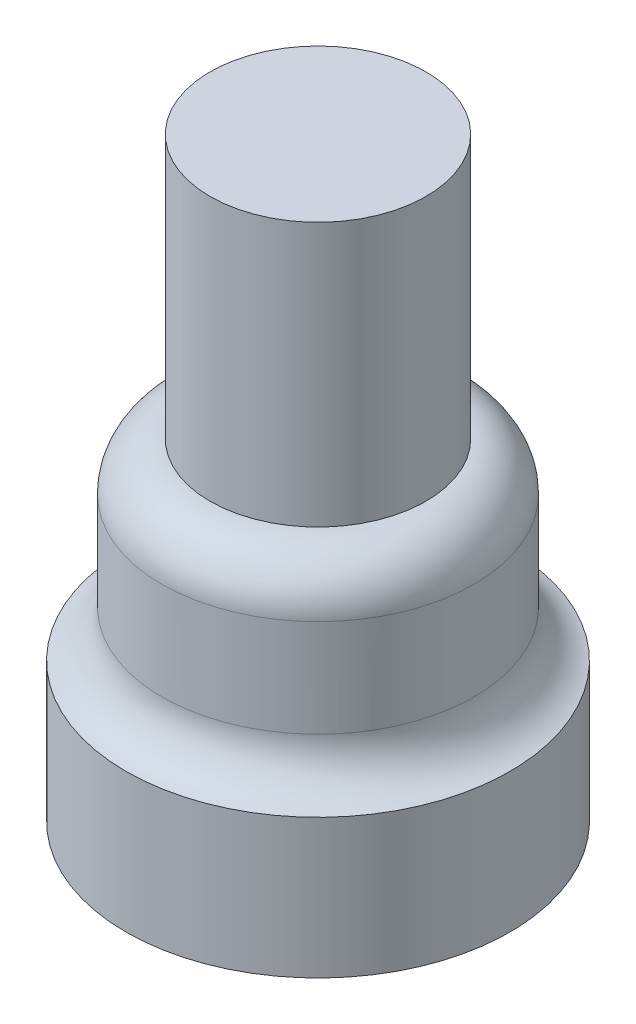
SolidWorks part; units mm, degrees
ref_plane "Front Plane" through (0, 0, 0) normal (0, 0, 1) x (1, 0, 0)
ref_plane "Top Plane" through (0, 0, 0) normal (0, 1, 0) x (1, 0, 0)
ref_plane "Right Plane" through (0, 0, 0) normal (1, 0, 0) x (0, 0, -1)
sketch "Sketch1" plane through (0, 0, 0) normal (0, 1, 0) x (1, 0, 0)
  circle A0 centre (0, 0) radius 8
extrude "Boss-Extrude1" add sketch "Sketch1" along normal blind 5.8
sketch "Sketch2" plane through (0, 5.8, 0) normal (0, 1, 0) x (-1, 0, 0)
  circle A0 centre (0, 0) radius 6.5
extrude "Boss-Extrude2" add sketch "Sketch2" along normal blind 8
sketch "Sketch3" plane through (0, 0, 0) normal (0, -1, 0) x (1, 0, 0)
  circle A0 centre (0, 0) radius 6
extrude "Cut-Extrude1" cut sketch "Sketch3" against normal blind 5.8
sketch "Sketch4" plane through (0, 5.8, 0) normal (0, -1, 0) x (1, 0, 0)
  circle A0 centre (0, 0) radius 4.5
extrude "Cut-Extrude2" cut sketch "Sketch4" against normal blind 7
sketch "Sketch5" plane through (0, 13.8, 0) normal (0, 1, 0) x (-1, 0, 0)
  circle A0 centre (0, 0) radius 4.5
  point P2 (0, 0)
extrude "Boss-Extrude3" add sketch "Sketch5" along normal blind 11
fillet "Fillet1" radius 2 2 edges at (0, 5.8, 6.5) (0, 13.8, 6.5)
